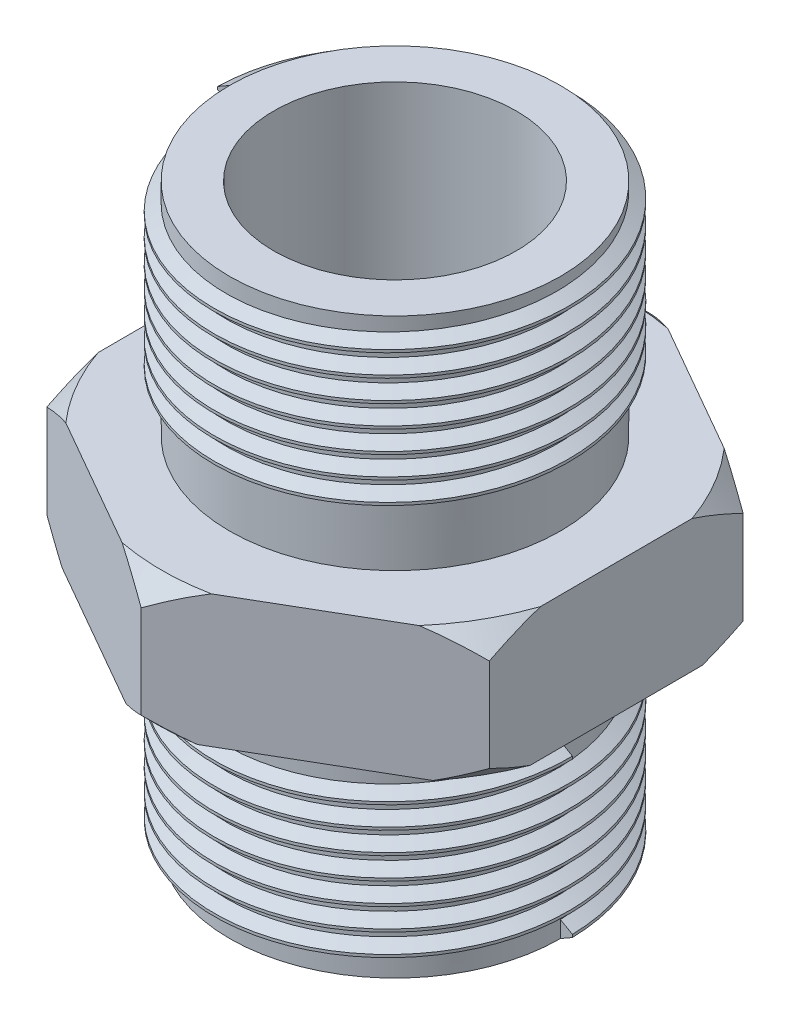
SolidWorks part; units mm, degrees
material "Free-Cutting Brass, UNS C36000"
ref_plane "Front Plane" through (0, 0, 0) normal (0, 0, 1) x (1, 0, 0)
ref_plane "Top Plane" through (0, 0, 0) normal (0, 1, 0) x (1, 0, 0)
ref_plane "Right Plane" through (0, 0, 0) normal (1, 0, 0) x (0, 0, -1)
sketch "Sketch1" plane through (0, 0, 0) normal (0, 0, 1) x (1, 0, 0)
  line L0 (0, 0) -> (0, 13) construction
  line L1 (7.5, -13) -> (7.5, 13)
  line L2 (7.5, 13) -> (5.5, 13)
  line L3 (5.5, 13) -> (5.5, -13)
  line L4 (5.5, -13) -> (7.5, -13)
  point P6 (7.5, 0)
  dimension "D1" = 5.5
  dimension "D2" = 26
  dimension "D3" = 2
revolve "Revolve1" add sketch "Sketch1" angle 360 about L0
sketch "Sketch2" plane through (0, 0, 0) normal (0, 1, 0) x (1, 0, 0)
  line L1 (-10.0181, 5.7421) -> (-9.9818, -5.8049)
  line L2 (-9.9818, -5.8049) -> (0.0363, -11.5469)
  line L3 (0.0363, -11.5469) -> (10.0181, -5.7421)
  line L4 (10.0181, -5.7421) -> (9.9818, 5.8049)
  line L5 (9.9818, 5.8049) -> (-0.0363, 11.5469)
  line L6 (-0.0363, 11.5469) -> (-10.0181, 5.7421)
  circle A0 centre (0, 0) radius 10 construction
  circle A2 centre (0, 0) radius 5.5
  dimension "D1" = 20
extrude "Boss-Extrude1" add sketch "Sketch2" along normal mid plane 6
thread "Thread1" pitch 1 method extrude profile "Thread Profile1" start angle 0, offset 0, length 7, pitch 1, diameter 15
ref_plane "Plane1" through (-7.5, 13, 0) normal (0, 0, 1) x (-1, 0, 0)
sketch "Thread Profile1" plane through (-7.5, 13, 0) normal (0, 0, 1) x (-1, 0, 0)
  line L0 (0, 0) -> (0, 1) construction
  line L1 (0, 0) -> (0.5413, 0.3125)
  line L2 (0.5413, 0.3125) -> (0.5413, 0.4375)
  line L3 (0.5413, 0.4375) -> (0, 0.75)
  line L4 (0.5413, 0.375) -> (0, 0.375) construction
  line L11 (0, 0) -> (0, 0.75)
  point P2 (0, 0)
  dimension "Pitch" = 1
  dimension "Profile_Angle" = 60
  dimension "Profile_Land" = 0.125
  dimension "Profile_Height" = 0.5413
thread "Thread2" pitch 1 method extrude profile "Thread Profile2" start angle 0, offset 0, length 7, pitch 1, diameter 15
ref_plane "Plane2" through (7.5, -13, 0) normal (0, 0, 1) x (1, 0, 0)
sketch "Thread Profile2" plane through (7.5, -13, 0) normal (0, 0, 1) x (1, 0, 0)
  line L0 (0, 0) -> (0, 1) construction
  line L1 (0, 0) -> (0.5413, 0.3125)
  line L2 (0.5413, 0.3125) -> (0.5413, 0.4375)
  line L3 (0.5413, 0.4375) -> (0, 0.75)
  line L4 (0.5413, 0.375) -> (0, 0.375) construction
  line L11 (0, 0) -> (0, 0.75)
  point P2 (0, 0)
  dimension "Pitch" = 1
  dimension "Profile_Angle" = 60
  dimension "Profile_Land" = 0.125
  dimension "Profile_Height" = 0.5413
sketch "Sketch10" plane through (0, 0, 0) normal (1, 0, 0) x (0, 0, -1)
  line L0 (0, 0) -> (0, 5.1669) construction
  line L10 (10.091, -3.6464) -> (12.0871, -1.6503)
  line L11 (12.0871, -1.6503) -> (12.0871, -3.6464)
  line L12 (12.0871, -3.6464) -> (10.091, -3.6464)
  line L13 (12.8448, 0.7329) -> (9.3228, 4.2549)
  line L14 (9.3228, 4.2549) -> (12.8448, 4.2549)
  line L15 (12.8448, 4.2549) -> (12.8448, 0.7329)
  point P9 (11.0838, 2.4939)
revolve "Cut-Revolve1" cut sketch "Sketch10" angle 360 about L0
ref_axis "Axis1" through (0, 20.5281, 0) along (0, -1, 0)
